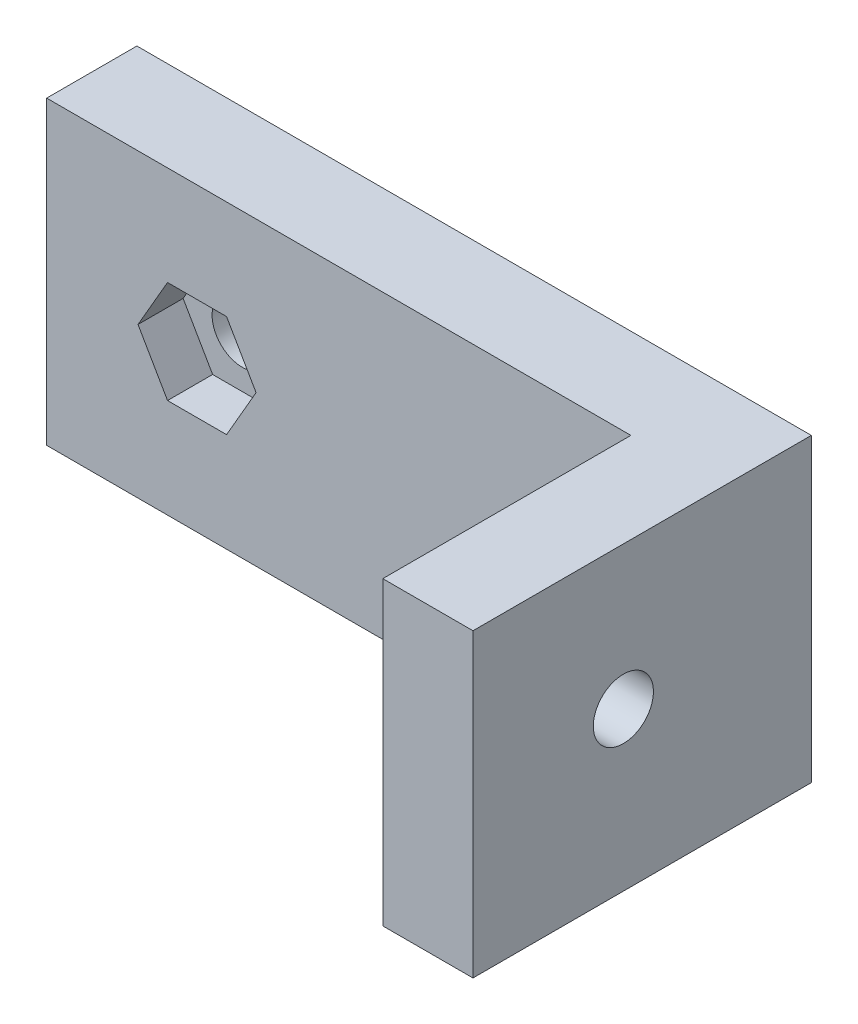
SolidWorks part; units mm, degrees
material "ABS"
ref_plane "Front Plane" through (0, 0, 0) normal (0, 0, 1) x (1, 0, 0)
ref_plane "Top Plane" through (0, 0, 0) normal (0, 1, 0) x (1, 0, 0)
ref_plane "Right Plane" through (0, 0, 0) normal (1, 0, 0) x (0, 0, -1)
sketch "Sketch1" plane through (0, 0, 0) normal (0, 0, 1) x (1, 0, 0)
  line L0 (169.7, 110.2) -> (169.7, 86.2) construction
  line L1 (169.7, -7.5) -> (124.85, -7.5)
  line L2 (169.7, -7.5) -> (169.7, 12.5)
  line L3 (169.7, 12.5) -> (124.85, 12.5)
  line L4 (124.85, -7.5) -> (124.85, 12.5)
  line L5 (169.7, -7.5) -> (124.85, 12.5) construction
  line L6 (169.7, 12.5) -> (124.85, -7.5) construction
  line L8 (130.924, 2.5) -> (132.887, -0.9)
  line L9 (132.887, -0.9) -> (136.813, -0.9)
  line L10 (136.813, -0.9) -> (138.776, 2.5)
  line L11 (138.776, 2.5) -> (136.813, 5.9)
  line L12 (136.813, 5.9) -> (132.887, 5.9)
  line L13 (132.887, 5.9) -> (130.924, 2.5)
  circle A0 centre (134.85, 2.5) radius 2
  circle A1 centre (134.85, 2.5) radius 3.4 construction
  point P4 (147.275, 2.5)
  point P10 (134.85, 5.9)
  dimension "D2" = 10
  dimension "D3" = 10
  dimension "D4" = 10
  dimension "D1" = 6.8
extrude "Boss-Extrude1" add sketch "Sketch1" along normal blind 3 contours L4 L1 L2 L3 L13 L12 L11 L10 L9 L8 | L12 L13 L8 L9 L10 L11 A0 region at (147.8556, 2.5, 0) region at (131.9955, 4.1481, 0)
extrude "Boss-Extrude2" add sketch "Sketch1<4>" along normal blind 3 from surface contours L4 L1 L2 L3 L13 L12 L11 L10 L9 L8 region at (147.8556, 2.5, 0) starting at face at (147.275, 2.5, 3)
sketch "Sketch1<4>" plane through (0, 0, 0) normal (0, 0, 1) x (1, 0, 0) same geometry as "Sketch1"
sketch "Sketch5" plane through (169.7, 0, 0) normal (-1, 0, 0) x (0, 0, 1)
  line L0 (6, 12.5) -> (0, 12.5) construction
  line L1 (6, -7.5) -> (22.5, -7.5)
  line L2 (6, -7.5) -> (6, 12.5)
  line L3 (6, 12.5) -> (22.5, 12.5)
  line L4 (22.5, -7.5) -> (22.5, 12.5)
  line L5 (6, -7.5) -> (22.5, 12.5) construction
  line L6 (6, 12.5) -> (22.5, -7.5) construction
  line L8 (12.5, -0.926) -> (15.9, 1.037)
  line L9 (15.9, 1.037) -> (15.9, 4.963)
  line L10 (15.9, 4.963) -> (12.5, 6.926)
  line L11 (12.5, 6.926) -> (9.1, 4.963)
  line L12 (9.1, 4.963) -> (9.1, 1.037)
  line L13 (9.1, 1.037) -> (12.5, -0.926)
  circle A0 centre (12.5, 3) radius 2
  circle A1 centre (12.5, 3) radius 3.4 construction
  point P7 (14.25, 2.5)
  dimension "D4" = 4
  dimension "D1" = 10
  dimension "D2" = 6.8
  dimension "D3" = 9.5
  dimension "D5" = 16.5
extrude "Boss-Extrude3" add sketch "Sketch5" along normal blind 3 contours L1 L4 L3 L2 L13 L12 L11 L10 L9 L8 | L12 L13 L8 L9 L10 L11 region at (169.7, 2.5, 6.2593) region at (169.7, 0.1455, 10.8519)
extrude "Boss-Extrude4" add sketch "Sketch5<3>" along normal blind 3 from surface contours L1 L4 L3 L2 L13 L12 L11 L10 L9 L8 region at (169.7, 2.5, 6.2593) starting at face at (166.7, 2.5, 14.25)
sketch "Sketch5<3>" plane through (169.7, 0, 0) normal (-1, 0, 0) x (0, 0, 1) same geometry as "Sketch5"
